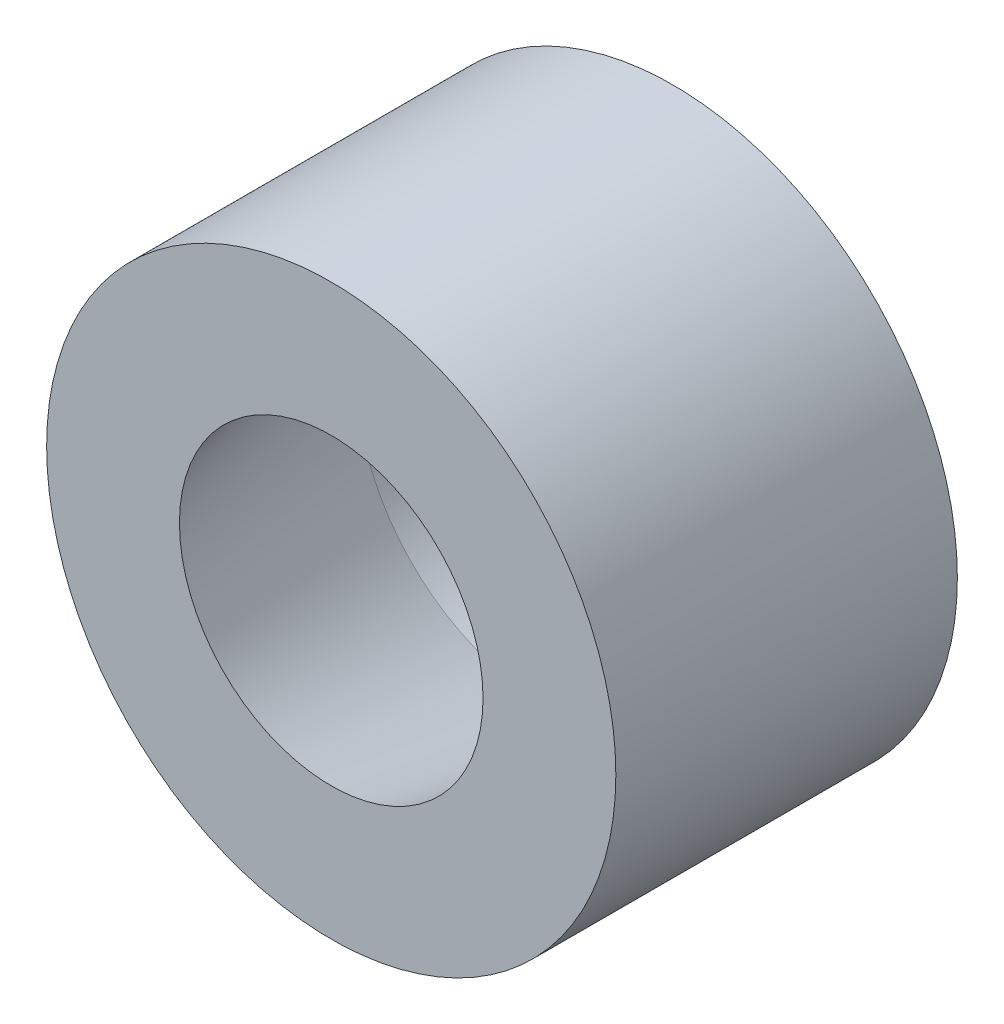
SolidWorks part; units mm, degrees
ref_plane "Front Plane" through (0, 0, 0) normal (0, 0, 1) x (1, 0, 0)
ref_plane "Top Plane" through (0, 0, 0) normal (0, 1, 0) x (1, 0, 0)
ref_plane "Right Plane" through (0, 0, 0) normal (1, 0, 0) x (0, 0, -1)
sketch "Sketch1" plane through (0, 0, 0) normal (0, 0, 1) x (1, 0, 0)
  circle A0 centre (0, 0) radius 15
  dimension "D1" = 30
extrude "Boss-Extrude1" add sketch "Sketch1" along normal blind 18
sketch "Sketch2" plane through (0, 0, 0) normal (0, 0, -1) x (-1, 0, 0)
  circle A0 centre (0, 0) radius 10
extrude "Cut-Extrude1" cut sketch "Sketch2" against normal blind 6.66
sketch "Sketch3" plane through (0, 0, 18) normal (0, 0, 1) x (1, 0, 0)
  circle A0 centre (0, 0) radius 8
extrude "Cut-Extrude2" cut sketch "Sketch3" against normal blind 100
chamfer "Chamfer1" distance 2 angle 80 1 edges at (-8, 0, 6.66) first distance on face at (-8, 0, 6.66)
